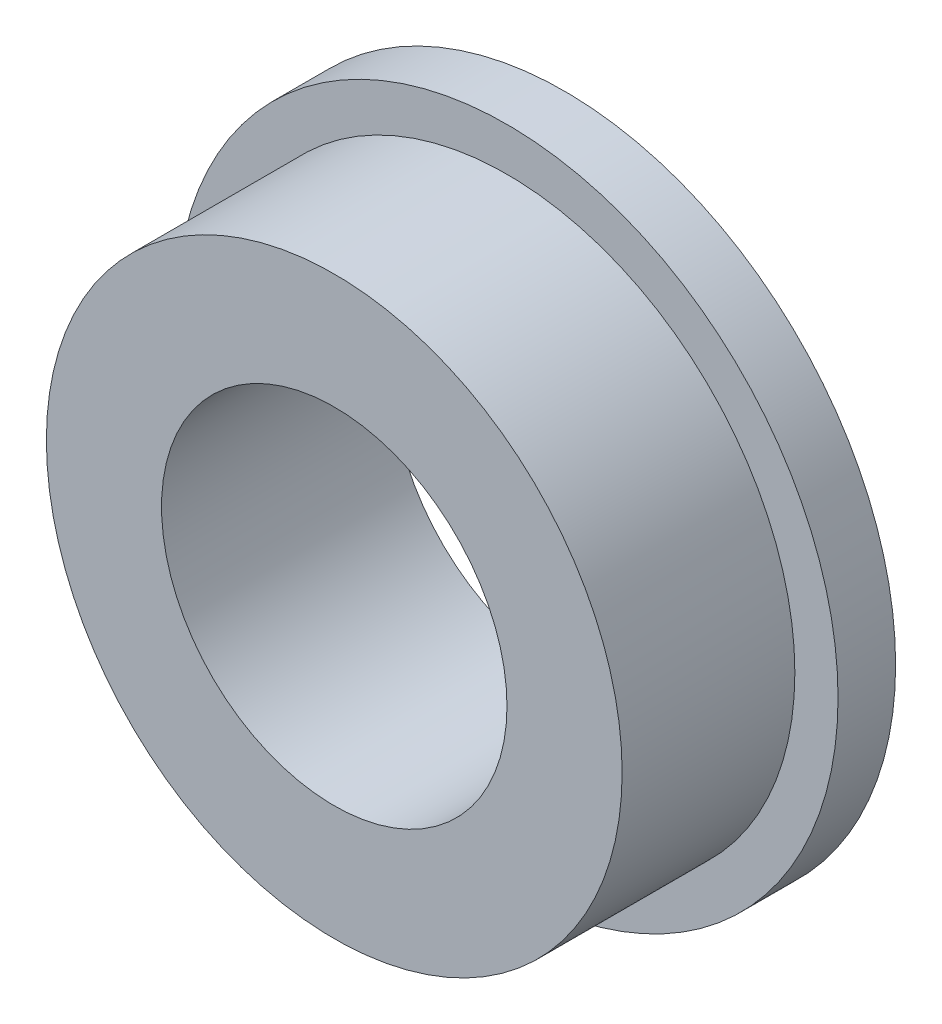
SolidWorks part; units mm, degrees
ref_plane "前视基准面" through (0, 0, 0) normal (0, 0, 1) x (1, 0, 0)
ref_plane "上视基准面" through (0, 0, 0) normal (0, 1, 0) x (1, 0, 0)
ref_plane "右视基准面" through (0, 0, 0) normal (1, 0, 0) x (0, 0, -1)
sketch "草图1" plane through (0, 0, 0) normal (0, 0, 1) x (1, 0, 0)
  circle A0 centre (0, 0) radius 3
  circle A1 centre (0, 0) radius 5
extrude "凸台-拉伸1" add sketch "草图1" along normal blind 4
sketch "草图2" plane through (0, 0, 0) normal (0, 0, 1) x (1, 0, 0)
  circle A0 centre (0, 0) radius 5.75
extrude "凸台-拉伸2" add sketch "草图2" along normal blind 0.9
sketch "草图3" plane through (0, 0, 0) normal (0, 0, 1) x (1, 0, 0)
  circle A0 centre (0, 0) radius 3
extrude "切除-拉伸2" cut sketch "草图3" along normal blind 9.9
extrude "凸台-拉伸3" add sketch "草图2<2>" along normal blind 1
sketch "草图2<2>" plane through (0, 0, 0) normal (0, 0, 1) x (1, 0, 0) same geometry as "草图2"
extrude "切除-拉伸3" cut sketch "草图3<2>" along normal blind 7
sketch "草图3<2>" plane through (0, 0, 0) normal (0, 0, 1) x (1, 0, 0) same geometry as "草图3"
